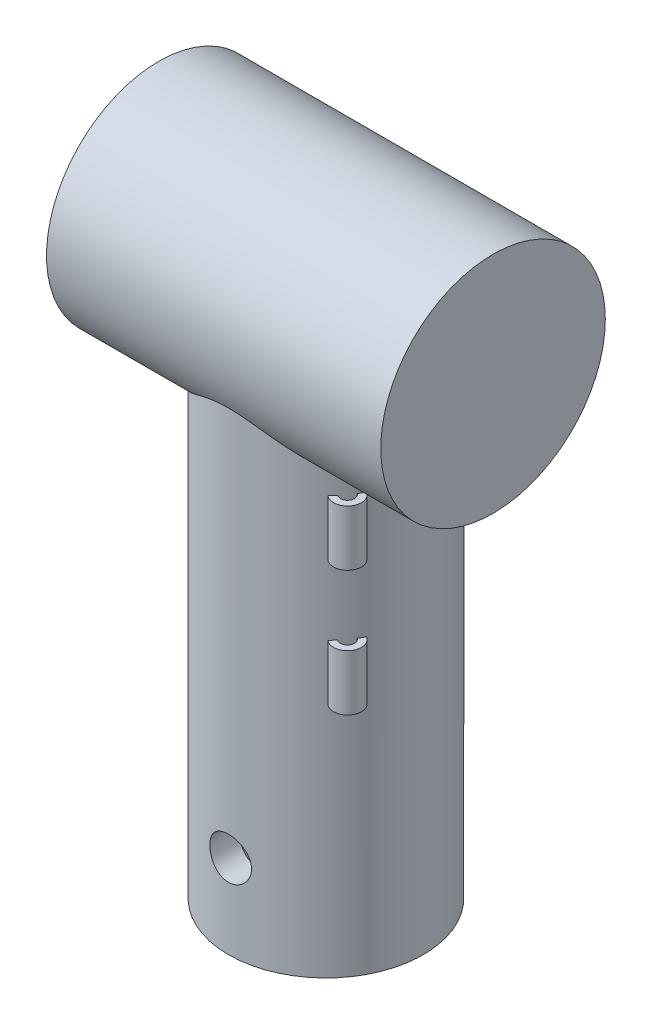
SolidWorks part; units mm, degrees
ref_plane "前视基准面" through (0, 0, 0) normal (0, 0, 1) x (1, 0, 0)
ref_plane "上视基准面" through (0, 0, 0) normal (0, 1, 0) x (1, 0, 0)
ref_plane "右视基准面" through (0, 0, 0) normal (1, 0, 0) x (0, 0, -1)
other "Configuration Table"
sketch "草图1" plane through (0, 0, 0) normal (0, 1, 0) x (1, 0, 0)
  circle A0 centre (0, 0) radius 7
  dimension "D1" = 14
extrude "凸台-拉伸1" add sketch "草图1" along normal blind 4
sketch "草图2" plane through (0, 4, 0) normal (0, 1, 0) x (1, 0, 0)
  circle A0 centre (0, 0) radius 7
  dimension "D1" = 14
extrude "凸台-拉伸2" add sketch "草图2" along normal blind 30
sketch "草图4" plane through (0, 34, 0) normal (0, 1, 0) x (1, 0, 0)
  circle A0 centre (5.6635, -4.114) radius 0.5
  circle A1 centre (0, 0) radius 7 construction
  circle A2 centre (5.6635, -4.114) radius 1
  dimension "D1" = 1
  dimension "D2" = 2
extrude "凸台-拉伸3" add sketch "草图4" against normal offset from surface (8 mm away) 8 up to face at (0, 34, 7)
ref_plane "基准面1" through (0, 21, 0) normal (0, -1, 0) x (-1, 0, 0)
sketch "草图5" plane through (0, 21, 0) normal (0, -1, 0) x (-1, 0, 0)
  arc A0 (-5.3553, -4.5078) -> (-5.0195, -4.879) centre (0, 0) ccw
  arc A7 (-5.9427, -3.6992) -> (-5.3553, -4.5078) centre (-5.6635, -4.114) ccw
  arc A8 (-6.1919, -3.265) -> (-5.0195, -4.879) centre (-5.6635, -4.114) ccw
  circle A9 centre (0, 0) radius 7 construction
  arc A10 (-6.1919, -3.265) -> (-5.9427, -3.6992) centre (0, 0) ccw
extrude "凸台-拉伸4" add sketch "草图5" along normal blind 4
sketch "草图9" plane through (0, 0, 0) normal (1, 0, 0) x (0, 0, -1)
  line L0 (0, 34) -> (0, 42) construction
  line L1 (7, 34) -> (-7, 34) construction
  circle A0 centre (0, 38) radius 8.0623
sketch "草图10" plane through (0, 34, 0) normal (0, 1, 0) x (1, 0, 0)
  arc A1 (5.3553, -4.5078) -> (5.9427, -3.6992) centre (5.6635, -4.114) ccw construction
  arc A2 (5.0195, -4.879) -> (6.1919, -3.265) centre (5.6635, -4.114) ccw construction
  arc A4 (5.3553, -4.5078) -> (5.9427, -3.6992) centre (5.6635, -4.114) ccw
  arc A5 (5.0195, -4.879) -> (6.1919, -3.265) centre (5.6635, -4.114) ccw
  arc A6 (5.0195, -4.879) -> (5.3553, -4.5078) centre (0, 0) ccw
  arc A7 (5.9427, -3.6992) -> (6.1919, -3.265) centre (0, 0) ccw
extrude "切除-拉伸1" cut sketch "草图10" against normal blind 4
extrude "凸台-拉伸5" add sketch "草图9" along normal blind 12 and the other way blind 12
ref_plane "基准面2" through (0, 12, 0) normal (0, -1, 0) x (-1, 0, 0)
sketch "草图11" plane through (0, 12, 0) normal (0, -1, 0) x (-1, 0, 0)
  circle A0 centre (0, 0) radius 4.9
  circle A1 centre (0, 0) radius 3
  dimension "D1" = 6
sketch "草图12" plane through (0, 0, 0) normal (0, -1, 0) x (1, 0, 0)
  circle A0 centre (0, 0) radius 5
  dimension "D1" = 10
extrude "切除-拉伸2" cut sketch "草图12" against normal blind 10
sketch "草图13" plane through (0, 0, 0) normal (0, 0, 1) x (1, 0, 0)
  circle A0 centre (0, 6) radius 1.5 construction
  circle A1 centre (0, 6) radius 1.5
extrude "切除-拉伸3" cut sketch "草图13" against normal through all both and the other way through all
